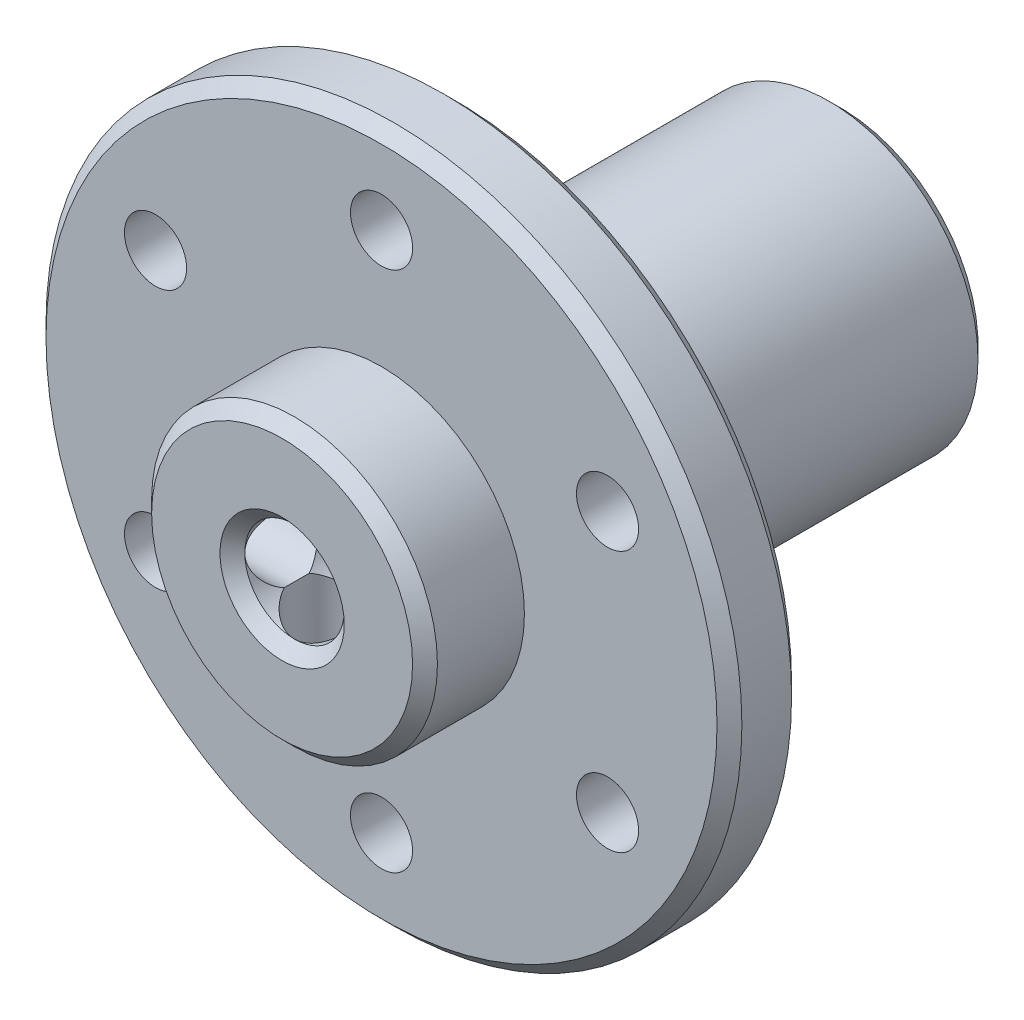
SolidWorks part; units mm, degrees
material "6061 合金"
ref_plane "前视基准面" through (0, 0, 0) normal (0, 0, 1) x (1, 0, 0)
ref_plane "上视基准面" through (0, 0, 0) normal (0, 1, 0) x (1, 0, 0)
ref_plane "右视基准面" through (0, 0, 0) normal (1, 0, 0) x (0, 0, -1)
sketch "草图1" plane through (0, 0, 0) normal (0, 0, 1) x (1, 0, 0)
  circle A0 centre (0, 0) radius 14
  circle A1 centre (0, 0) radius 2
  circle A2 centre (0, 0) radius 8.9266 construction
  dimension "D1" = 4
  dimension "D2" = 28
extrude "凸台-拉伸1" add sketch "草图1" along normal blind 3
sketch "草图2" plane through (0, 0, 3) normal (0, 0, 1) x (1, 0, 0)
  circle A0 centre (0, 0) radius 10.5 construction
  circle A1 centre (0, 10.5) radius 1.25
  dimension "D1" = 21
  dimension "D2" = 2.5
extrude "切除-拉伸1" cut sketch "草图2" against normal blind 4
cosmetic thread "孔螺蚊线1" parameters "D1"=3, "D2"=3
cosmetic thread "孔螺蚊线2" parameters "D2"=3
hole_wizard "M3 螺纹孔1" positions "3D草图1" profile "草图3" tap size "M3" standard "Gb" end condition through all
sketch3d "3D草图1"
  line L0 (0, 10.5, 0) -> (0, 10.5, 3) construction
  point P0 (0, 10.5, 3)
sketch "草图3" plane through (0, 10.5, 3) normal (1, 0, 0) x (0, -1, 0)
  line L0 (0, 0) -> (0, 3)
  line L1 (0, 3) -> (1.25, 3)
  line L2 (1.25, 3) -> (1.25, 0)
  line L5 (1.25, 0) -> (0, 0)
  line L11 (0, -6.35) -> (0, 107.95) construction
  dimension "通孔螺纹孔钻头直径" = 2.5
  dimension "通孔螺纹孔钻头深度" = 3
pattern_circular "阵列(圆周)1" count 6 over 360 about axis through (0, 0, 0) along (0, 0, 1) of "M3 螺纹孔1", "切除-拉伸1"
sketch "草图4" plane through (0, 0, 3) normal (0, 0, 1) x (1, 0, 0)
  circle A0 centre (0, 0) radius 5.75
  circle A1 centre (0, 0) radius 2
  circle A2 centre (0, 0) radius 2 construction
  dimension "D1" = 11.5
extrude "凸台-拉伸2" add sketch "草图4" along normal blind 4
sketch "草图5" plane through (0, 0, 0) normal (0, 0, -1) x (-1, 0, 0)
  circle A0 centre (0, 0) radius 6
  circle A1 centre (0, 0) radius 2 construction
  circle A2 centre (0, 0) radius 2
  dimension "D1" = 12
extrude "凸台-拉伸3" add sketch "草图5" along normal blind 15.5
sketch "草图6" plane through (0, 0, 0) normal (0, 1, 0) x (1, 0, 0)
  line L0 (0, -7) -> (0, -5) construction
  line L1 (-5.75, -7) -> (5.75, -7) construction
  circle A0 centre (0, -5) radius 1.5
  dimension "D1" = 3
  dimension "D2" = 2
extrude "切除-拉伸2" cut sketch "草图6" against normal blind 10
pattern_circular "阵列(圆周)2" count 2 every 90 about axis through (0, 0, 3) along (0, 0, -1) of "切除-拉伸2"
chamfer "倒角1" distance 0.5 angle 45 6 edges at (-2, 0, -15.5) (-6, 0, -15.5) (14, 0, 0) (14, 0, 3) (5.75, 0, 7) (2, 0, 7)
